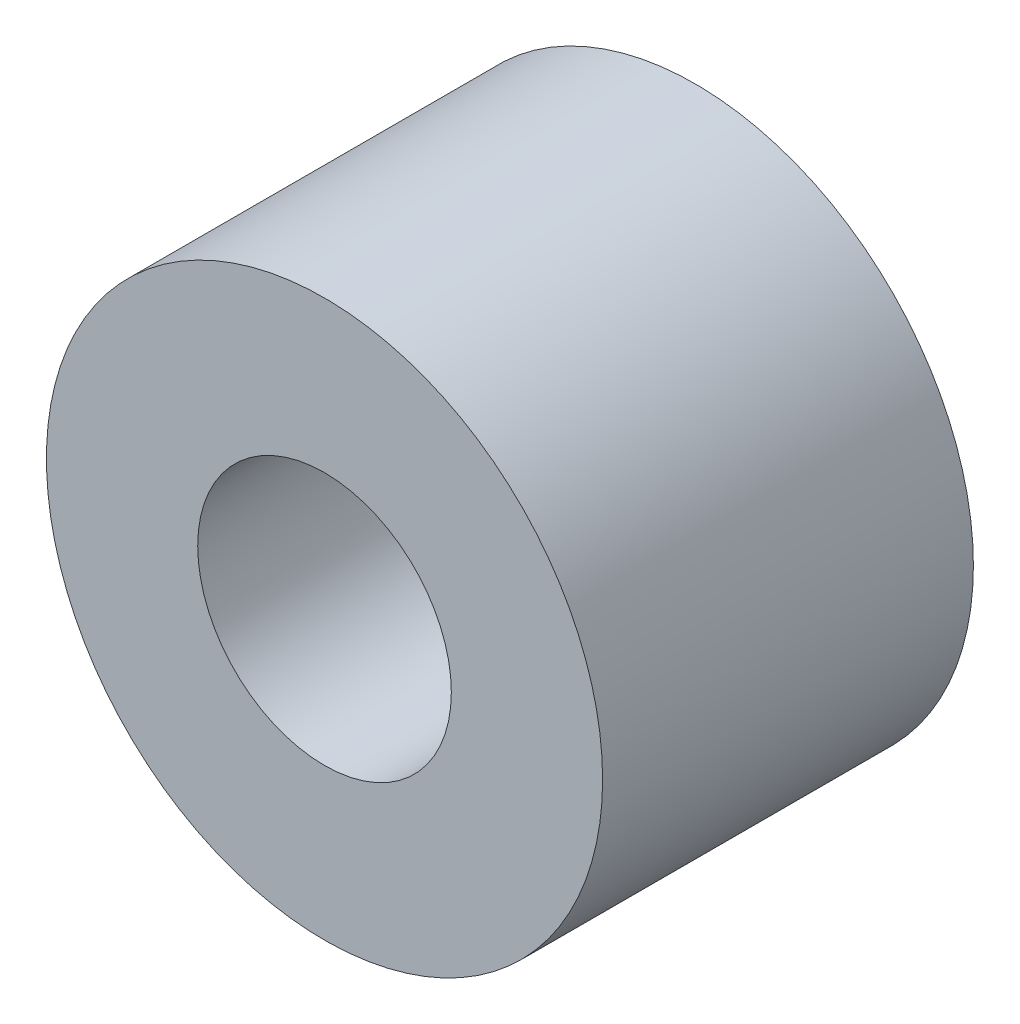
SolidWorks part; units mm, degrees
ref_plane "Front Plane" through (0, 0, 0) normal (0, 0, 1) x (1, 0, 0)
ref_plane "Top Plane" through (0, 0, 0) normal (0, 1, 0) x (1, 0, 0)
ref_plane "Right Plane" through (0, 0, 0) normal (1, 0, 0) x (0, 0, -1)
sketch "Sketch3" plane through (0, 0, 0) normal (0, 0, 1) x (1, 0, 0)
  circle A0 centre (0, 0) radius 2.1717 construction
  circle A1 centre (0, 0) radius 4.7625 construction
  point P6 (0, -2.1717)
  dimension "OD" = 9.525
  dimension "ID" = 4.3434
sketch "Sketch1" plane through (0, 0, 0) normal (1, 0, 0) x (0, 0, -1)
  line L0 (-3.175, -2.1717) -> (-3.175, 2.1717) construction
  line L1 (3.175, -4.7625) -> (-3.175, -4.7625) construction
  line L2 (3.175, -4.7625) -> (3.175, 4.7625) construction
  line L3 (3.175, 4.7625) -> (-3.175, 4.7625) construction
  line L4 (-3.175, -4.7625) -> (-3.175, 4.7625) construction
  line L5 (0, 4.7625) -> (0, -4.7625) construction
  line L6 (3.175, 0) -> (-3.175, 0) construction
  point P0 (0, 0)
  point P7 (-3.175, 0)
  dimension "OD" = 9.525
  dimension "ID" = 4.3434
sketch "Sketch2" plane through (0, 0, 0) normal (0, 0, 1) x (1, 0, 0)
  circle A0 centre (0, 0) radius 4.7625
  circle A1 centre (0, 0) radius 2.1717
extrude "Extrude1" add sketch "Sketch2" along normal up to vertex and the other way up to vertex up to point (0, -4.7625, 3.175) other way up to point (0, 4.7625, -3.175)
ref_axis "Center Axis1" through (0, 0, -31.4325) along (0, 0, 1)
ref_plane "Contact Plane1" through (0, 0, -3.175) normal (0, 0, 1) x (1, 0, 0)
ref_plane "Contact Plane2" through (0, 0, 3.175) normal (0, 0, 1) x (1, 0, 0)
equation "\"ID@Sketch1\" = \"ID@Sketch3\""
equation "\"OD@Sketch1\" = \"OD@Sketch3\""
